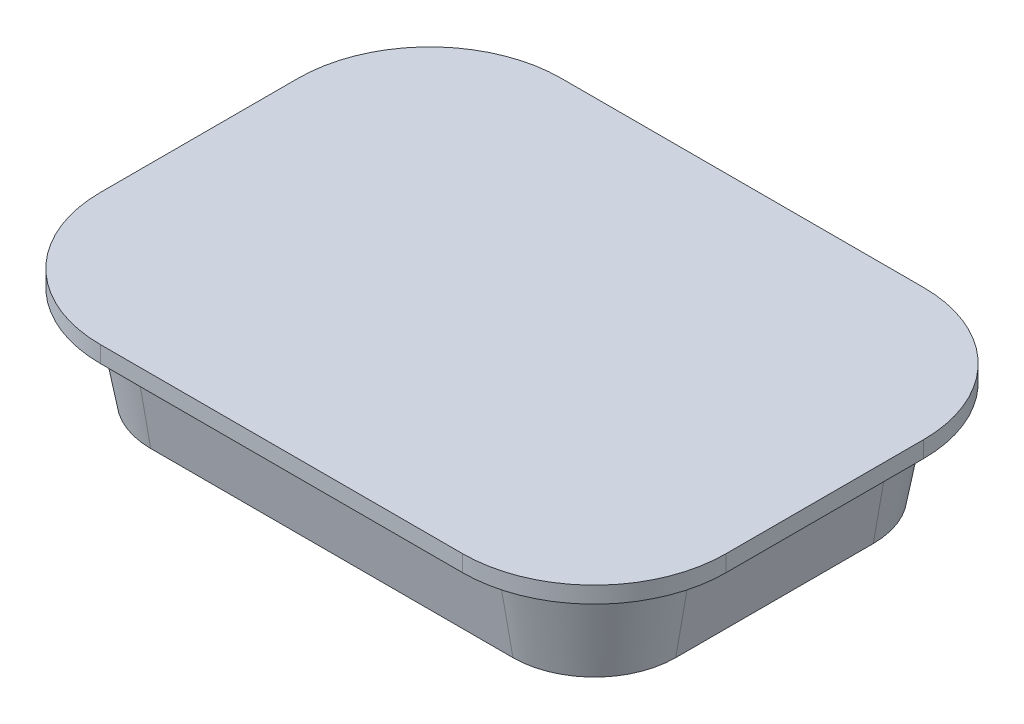
SolidWorks part; units mm, degrees
ref_plane "Front Plane" through (0, 0, 0) normal (0, 0, 1) x (1, 0, 0)
ref_plane "Top Plane" through (0, 0, 0) normal (0, 1, 0) x (1, 0, 0)
ref_plane "Right Plane" through (0, 0, 0) normal (1, 0, 0) x (0, 0, -1)
sketch "Sketch1" plane through (0, 0, 0) normal (0, 1, 0) x (1, 0, 0)
  line L0 (-55, 70) -> (55, 70)
  line L1 (-55, -60) -> (55, -60)
  line L2 (-85, -30) -> (-85, 30)
  line L3 (-55, 60) -> (55, 60)
  line L4 (85, -30) -> (85, 30)
  line L5 (-85, -60) -> (85, 60) construction
  line L6 (-85, 60) -> (85, -60) construction
  line L7 (95, -30) -> (95, 30)
  line L8 (-55, -70) -> (55, -70)
  line L9 (-95, -30) -> (-95, 30)
  arc A0 (55, 60) -> (85, 30) centre (55, 30) cw
  arc A1 (55, -60) -> (85, -30) centre (55, -30) ccw
  arc A2 (-55, -60) -> (-85, -30) centre (-55, -30) cw
  arc A3 (-85, 30) -> (-55, 60) centre (-55, 30) cw
  arc A4 (55, 70) -> (95, 30) centre (55, 30) cw
  arc A5 (55, -70) -> (95, -30) centre (55, -30) ccw
  arc A6 (-55, -70) -> (-95, -30) centre (-55, -30) cw
  arc A7 (-95, 30) -> (-55, 70) centre (-55, 30) cw
  point P0 (0, 0)
  dimension "Inside_Fillet" = 30
  dimension "D1" = 170
  dimension "D2" = 120
  dimension "D3" = 10
extrude "Boss-Extrude1" add sketch "Sketch1" along normal blind 5 contours A7 L9 A6 L8 A5 L7 A4 L0 L2 A3 L3 A0 L4 A1 L1 A2 | A2 L2 A3 L3 A0 L4 A1 L1 region at (0, 0, -67.6399)
extrude "Boss-Extrude2" add sketch "Sketch1<4>" against normal blind 30 draft 10 contours A2 L2 A3 L3 A0 L4 A1 L1
sketch "Sketch1<4>" plane through (0, 0, 0) normal (0, 1, 0) x (1, 0, 0) same geometry as "Sketch1"
equation "\"Food Length\" = 170"
equation "\"D1@Sketch1\"=\"Food Length\""
equation "\"Food Width\"= 120"
equation "\"D2@Sketch1\"=\"Food Width\""
equation "\"Lip_Thickness\"=5"
equation "\"D1@Boss-Extrude1\"=\"Lip_Thickness\""
equation "\"Lip_Width\"=10"
equation "\"D3@Sketch1\"=\"Lip_Width\""
